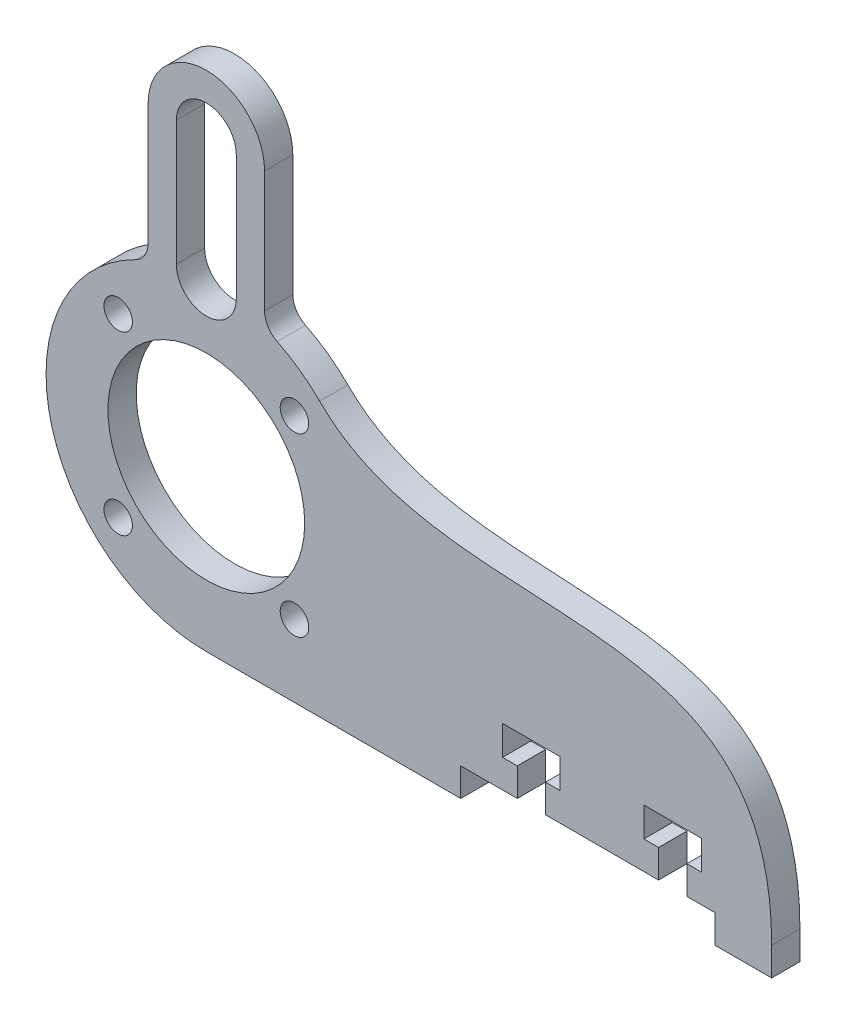
SolidWorks part; units mm, degrees
ref_plane "Front Plane" through (0, 0, 0) normal (0, 0, 1) x (1, 0, 0)
ref_plane "Top Plane" through (0, 0, 0) normal (0, 1, 0) x (1, 0, 0)
ref_plane "Right Plane" through (0, 0, 0) normal (1, 0, 0) x (0, 0, -1)
sketch "Sketch1" plane through (0, 0, 0) normal (0, 0, 1) x (1, 0, 0)
  line L0 (0, 0) -> (12.7277, 12.7277) construction
  line L1 (57.15, -17.9997) -> (63.5, -17.9997)
  line L2 (63.5, -17.9997) -> (63.5, -14.8247)
  line L3 (36.8115, -11.3561) -> (-11.3563, 36.8117) construction
  line L4 (28.575, -17.9997) -> (28.575, -14.8247)
  line L5 (28.575, -14.8247) -> (34.925, -14.8247)
  line L6 (34.925, -14.8247) -> (34.925, -11.6497)
  line L7 (34.925, -11.6497) -> (33.274, -11.6497)
  line L8 (33.274, -11.6497) -> (33.274, -8.3477)
  line L9 (33.274, -8.3477) -> (39.751, -8.3477)
  line L10 (39.751, -8.3477) -> (39.751, -11.6497)
  line L11 (39.751, -11.6497) -> (38.1, -11.6497)
  line L12 (38.1, -11.6497) -> (38.1, -14.8247)
  line L13 (38.1, -14.8247) -> (50.8, -14.8247)
  line L14 (50.8, -14.8247) -> (50.8, -11.6497)
  line L15 (50.8, -11.6497) -> (49.149, -11.6497)
  line L16 (49.149, -11.6497) -> (49.149, -8.3477)
  line L17 (49.149, -8.3477) -> (55.626, -8.3477)
  line L18 (55.626, -8.3477) -> (55.626, -11.6497)
  line L19 (55.626, -11.6497) -> (53.975, -11.6497)
  line L20 (53.975, -11.6497) -> (53.975, -14.8247)
  line L21 (53.975, -14.8247) -> (57.15, -14.8247)
  line L22 (57.15, -14.8247) -> (57.15, -17.9997)
  line L23 (0, -17.9997) -> (28.575, -17.9997)
  line L24 (63.5, -14.8247) -> (63.5, 40.5308) construction
  line L25 (-6.5405, 18.4235) -> (-6.5405, 32.0094)
  line L26 (6.5405, 18.4235) -> (6.5405, 32.0094)
  line L27 (0, 32.0094) -> (0, 17.9997) construction
  line L28 (3.3655, 32.0094) -> (3.3655, 17.9997)
  line L29 (-3.3655, 32.0094) -> (-3.3655, 17.9997)
  circle A0 centre (0, 0) radius 11.049
  arc A1 (12.7277, 12.7277) -> (7.9576, 16.1452) centre (0, 0) ccw
  circle A2 centre (9.8998, 9.8998) radius 1.6
  circle A3 centre (9.8998, -9.8998) radius 1.6
  circle A4 centre (-9.8998, -9.8998) radius 1.6
  circle A5 centre (-9.8998, 9.8998) radius 1.6
  arc A6 (-6.5405, 32.0094) -> (6.5405, 32.0094) centre (0, 32.0094) cw
  arc A7 (-7.9576, 16.1452) -> (0, -17.9997) centre (0, 0) ccw
  arc A8 (6.5405, 18.4235) -> (7.9576, 16.1452) centre (9.0805, 18.4235) ccw
  arc A9 (-6.5405, 18.4235) -> (-7.9576, 16.1452) centre (-9.0805, 18.4235) cw
  arc A10 (3.3655, 32.0094) -> (-3.3655, 32.0094) centre (0, 32.0094) ccw
  arc A11 (-3.3655, 17.9997) -> (3.3655, 17.9997) centre (0, 17.9997) ccw
  spline S0 degree 3 poles (12.7277, 12.7277) (27.4236, -1.9681) (63.5, 17.2471) (63.5, -14.8247) knots 0 0 0 0 1 1 1 1
  point P46 (6.5405, 16.7694)
  point P49 (-6.5405, 16.7694)
  point P52 (0, 25.0045)
  dimension "D1" = 22.098
  dimension "D2" = 35.9994
  dimension "D4" = 3.2
  dimension "D6" = 63.5
  dimension "D7" = 3.302
  dimension "D18" = 2.54
  dimension "D19" = 3.3655
  dimension "D3" = 14.0005
  dimension "D8" = 6.477
  dimension "D9" = 3.175
  dimension "D10" = 12.7
  dimension "D11" = 3.175
  dimension "D12" = 9.652
  dimension "D13" = 6.35
  dimension "D14" = 3.175
  dimension "D15" = 6.35
  dimension "D16" = 13.081
  dimension "D17" = 15.24
  dimension "D5" = 4
extrude "Boss-Extrude1" add sketch "Sketch1" along normal blind 3.175
